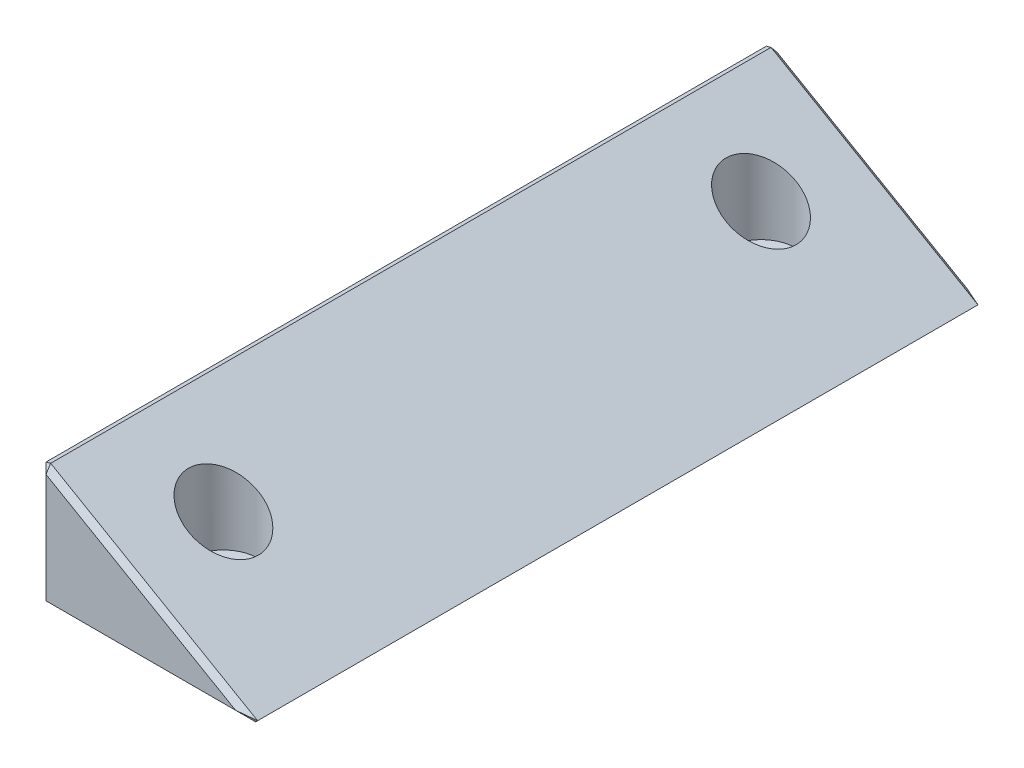
SolidWorks part; units mm, degrees
material "PET"
ref_plane "Front Plane" through (0, 0, 0) normal (0, 0, 1) x (1, 0, 0)
ref_plane "Top Plane" through (0, 0, 0) normal (0, 1, 0) x (1, 0, 0)
ref_plane "Right Plane" through (0, 0, 0) normal (1, 0, 0) x (0, 0, -1)
sketch "Sketch1" plane through (0, 0, 0) normal (0, 0, 1) x (1, 0, 0)
  line L0 (0, 0) -> (0, -11.547)
  line L1 (0, -11.547) -> (20, -11.547)
  line L2 (20, -11.547) -> (0, 0)
  dimension "D1" = 30
  dimension "D2" = 20
  dimension "D3" = 11.547
extrude "Boss-Extrude1" add sketch "Sketch1" along normal mid plane 68
hole_wizard "CBORE for M3 Hex Socket Head Cap Screw1" positions "Sketch2" profile "Sketch3" counterbore size "M3" standard "ISO" end condition through all
sketch "Sketch2" plane through (0, 0, 0) normal (0, 1, 0) x (1, 0, 0)
  line L0 (8, 25) -> (8, -25) construction
  line L2 (0, 0) -> (8, 0) construction
  line L4 (20, -34) -> (20, 34) construction
  point P0 (8, -25)
  point P2 (8, 25)
  dimension "D1" = 50
  dimension "D2" = 12
sketch "Sketch3" plane through (8, 0, 25) normal (1, 0, 0) x (0, 0, 1)
  line L0 (0, 0) -> (0, 11.547)
  line L1 (0, 11.547) -> (1.7, 11.547)
  line L3 (1.7, 11.547) -> (1.7, 10)
  line L4 (1.7, 10) -> (3.25, 10)
  line L5 (3.25, 10) -> (3.25, 0)
  line L7 (3.25, 0) -> (0, 0)
  line L11 (0, -6.35) -> (0, 107.95) construction
  dimension "Thru Hole Dia." = 3.4
  dimension "Thru Hole Depth" = 11.547
  dimension "C'Bore Dia." = 6.5
  dimension "C'Bore Depth" = 10
chamfer "Chamfer1" distance 0.5 angle 45 11 edges at (0, 0, 0) (20, -11.547, 0) (8, -11.547, -23.3) (8, -11.547, 26.7) (0, -5.7735, 34) (0, -5.7735, -34) (10, -5.7735, -34) (10, -11.547, -34) (0, -11.547, 0) (10, -11.547, 34) (10, -5.7735, 34)
